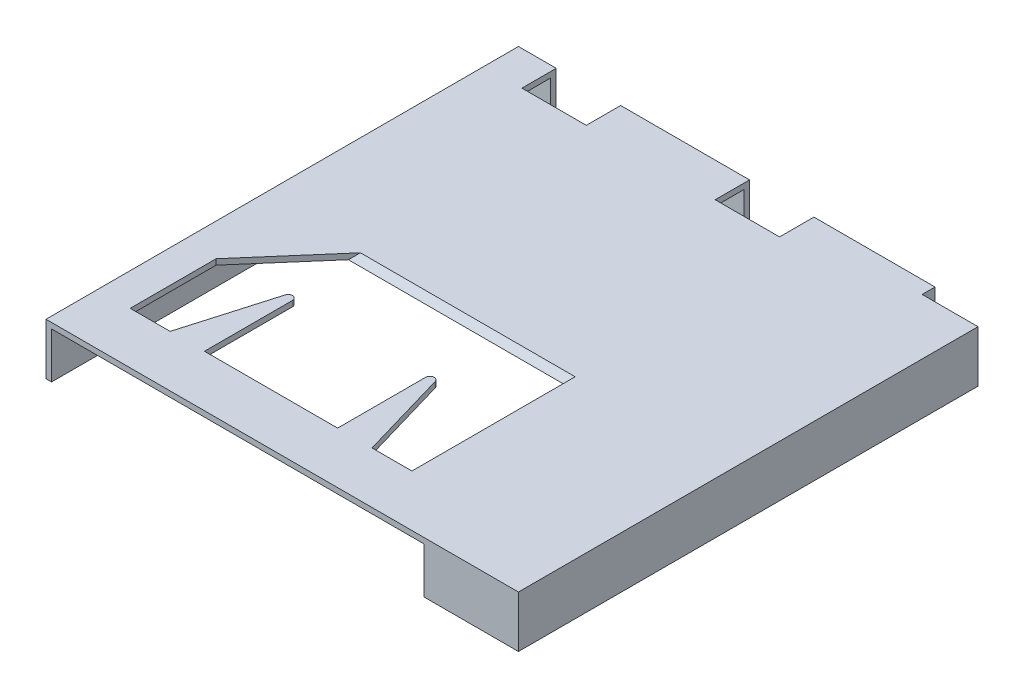
SolidWorks part; units mm, degrees
ref_plane "Front Plane" through (0, 0, 0) normal (0, 0, 1) x (1, 0, 0)
ref_plane "Top Plane" through (0, 0, 0) normal (0, 1, 0) x (1, 0, 0)
ref_plane "Right Plane" through (0, 0, 0) normal (1, 0, 0) x (0, 0, -1)
ref_plane "Plane1" through (0, 1.524, 0) normal (0, 1, 0) x (-1, 0, 0)
sketch "Sketch1" plane through (0, 1.524, 0) normal (0, 1, 0) x (-1, 0, 0)
  line L0 (-1.7526, -6.985) -> (-1.7526, 6.985)
  line L1 (-1.7526, 6.985) -> (-6.985, 6.985)
  line L2 (-6.985, 6.985) -> (-6.985, -6.985)
  line L3 (-6.985, -6.985) -> (-1.7526, -6.985)
extrude "Boss-Extrude1" add sketch "Sketch1" against normal blind 1.524
ref_plane "Plane2" through (0, 0, 6.985) normal (0, 0, 1) x (1, 0, 0)
sketch "Sketch2" plane through (0, 0, 6.985) normal (0, 0, 1) x (1, 0, 0)
  line L0 (-5.8674, 1.3589) -> (1.7526, 1.3589)
  line L1 (1.7526, 1.3589) -> (1.7526, 1.524)
  line L2 (1.7526, 1.524) -> (-6.985, 1.524)
  line L3 (-6.985, 1.524) -> (-6.985, 0)
  line L4 (-6.985, 0) -> (-5.8674, 0)
  line L5 (-5.8674, 0) -> (-5.8674, 1.3589)
extrude "Boss-Extrude2" add sketch "Sketch2" against normal blind 12.954
sketch "Sketch3" plane through (0, 0, -5.969) normal (0, 0, -1) x (-1, 0, 0)
  line L0 (6.985, 1.524) -> (6.985, 0)
  line L1 (6.985, 0) -> (5.8674, 0)
  line L2 (5.8674, 0) -> (5.8674, 1.524)
  line L3 (5.8674, 1.524) -> (6.985, 1.524)
extrude "Boss-Extrude3" add sketch "Sketch3" along normal blind 1.016
sketch "Sketch4" plane through (0, 0, -5.969) normal (0, 0, -1) x (-1, 0, 0)
  line L0 (0.1524, 1.3589) -> (0.1524, 1.524)
  line L1 (0.1524, 1.524) -> (3.9624, 1.524)
  line L2 (3.9624, 1.524) -> (3.9624, 1.3589)
  line L3 (3.9624, 1.3589) -> (0.1524, 1.3589)
extrude "Boss-Extrude4" add sketch "Sketch4" along normal blind 1.016
sketch "Sketch5" plane through (0, 1.3589, 0) normal (0, -1, 0) x (1, 0, 0)
  line L0 (-3.9624, -6.985) -> (-3.9624, -6.8199)
  line L1 (-3.9624, -6.8199) -> (-0.1524, -6.8199)
  line L2 (-0.1524, -6.8199) -> (-0.1524, -6.985)
  line L3 (-0.1524, -6.985) -> (-3.9624, -6.985)
extrude "Boss-Extrude5" add sketch "Sketch5" along normal blind 1.3589
sketch "Sketch6" plane through (-5.8674, 0, 0) normal (1, 0, 0) x (0, 0, -1)
  line L0 (6.8199, 1.3589) -> (-6.985, 1.3589)
  line L1 (-6.985, 1.3589) -> (-6.985, 0)
  line L2 (-6.985, 0) -> (6.8199, 0)
  line L3 (6.8199, 0) -> (6.8199, 1.3589)
extrude "Cut-Extrude1" cut sketch "Sketch6" against normal blind 0.9525
sketch "Sketch7" plane through (1.7526, 0, 0) normal (-1, 0, 0) x (0, 0, 1)
  line L0 (-6.8199, 0) -> (6.985, 0)
  line L1 (6.985, 0) -> (6.985, 1.3589)
  line L2 (6.985, 1.3589) -> (-6.8199, 1.3589)
  line L3 (-6.8199, 1.3589) -> (-6.8199, 0)
extrude "Cut-Extrude2" cut sketch "Sketch7" against normal blind 2.4384
sketch "Sketch8" plane through (0, 1.524, 0) normal (0, 1, 0) x (-1, 0, 0)
  line L0 (-6.985, -6.985) -> (-5.334, -6.985)
  line L1 (-5.334, -6.985) -> (-5.334, -6.604)
  line L2 (-5.334, -6.604) -> (-6.985, -6.604)
  line L3 (-6.985, -6.604) -> (-6.985, -6.985)
extrude "Cut-Extrude3" cut sketch "Sketch8" against normal blind 1.524
sketch "Sketch9" plane through (0, 1.524, 0) normal (0, 1, 0) x (-1, 0, 0)
  line L0 (3.8227, 2.861) -> (3.8227, 5.461)
  line L1 (3.8227, 5.461) -> (-0.1143, 5.461)
  line L2 (-0.1143, 5.461) -> (-0.1143, 2.861)
  line L3 (-0.3632, 2.8255) -> (-1.1303, 5.461)
  line L4 (-1.1303, 5.461) -> (-2.3114, 5.461)
  line L5 (-2.3114, 5.461) -> (-2.3114, 1.778)
  line L6 (-2.3114, 1.778) -> (6.0198, 1.778)
  line L7 (6.0198, 1.778) -> (6.0198, 5.461)
  line L8 (6.0198, 5.461) -> (4.8387, 5.461)
  line L9 (4.8387, 5.461) -> (4.0716, 2.8255)
  arc A0 (-0.1143, 2.861) -> (-0.3632, 2.8255) centre (-0.2413, 2.861) cw
  arc A1 (4.0716, 2.8255) -> (3.8227, 2.861) centre (3.9497, 2.861) cw
extrude "Cut-Extrude4" cut sketch "Sketch9" against normal through all
chamfer "Chamfer1" distance 1.143 angle 40.914 1 edges at (-6.0198, 1.4414, 1.778)
chamfer "Chamfer2" distance 0.9906 angle 49.086 1 edges at (-1.3589, 1.524, 1.778)
